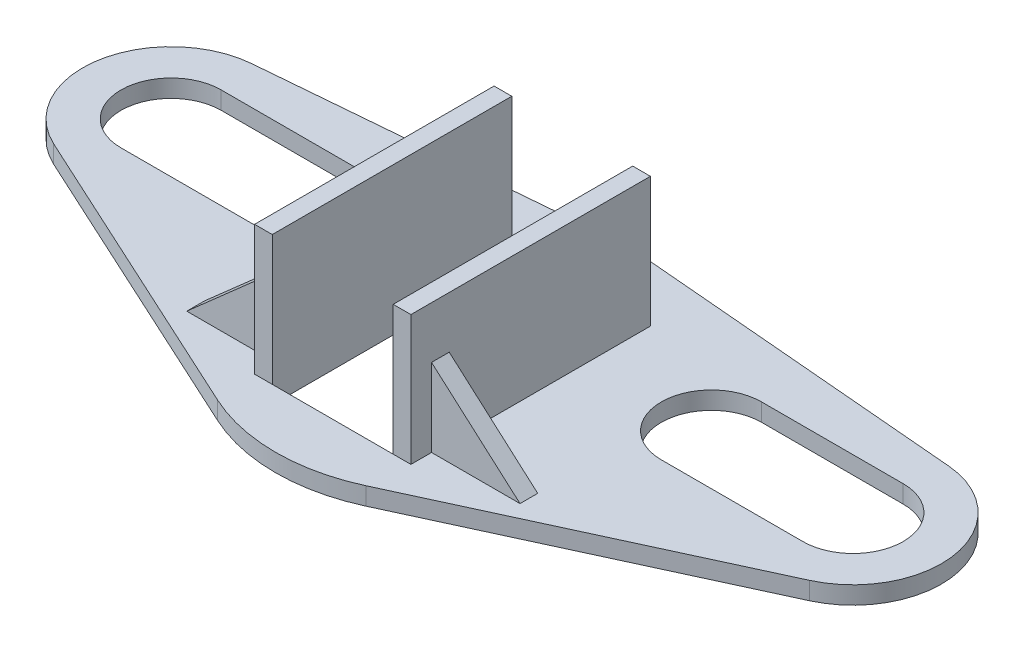
SolidWorks part; units mm, degrees
ref_plane "Front Plane" through (0, 0, 0) normal (0, 0, 1) x (1, 0, 0)
ref_plane "Top Plane" through (0, 0, 0) normal (0, 1, 0) x (1, 0, 0)
ref_plane "Right Plane" through (0, 0, 0) normal (1, 0, 0) x (0, 0, -1)
sketch "Sketch1" plane through (0, 0, 0) normal (0, 1, 0) x (1, 0, 0)
  line L0 (-57.8, 10.1) -> (-33.8, 10.1) construction
  line L1 (-10.25, -20.3) -> (10.25, -20.3)
  line L2 (-10.25, -20.3) -> (-10.25, 20.3)
  line L3 (-10.25, 20.3) -> (10.25, 20.3)
  line L4 (10.25, -20.3) -> (10.25, 20.3)
  line L5 (-10.25, -20.3) -> (10.25, 20.3) construction
  line L6 (-10.25, 20.3) -> (10.25, -20.3) construction
  line L7 (-57.8, 18.6) -> (-33.8, 18.6)
  line L8 (-57.8, 1.6) -> (-33.8, 1.6)
  line L9 (33.8, 10.1) -> (57.8, 10.1) construction
  line L10 (33.8, 18.6) -> (57.8, 18.6)
  line L11 (33.8, 1.6) -> (57.8, 1.6)
  line L12 (-59.0812, 25.0452) -> (-2.5624, 29.8904)
  line L13 (2.5624, 29.8904) -> (59.0812, 25.0452)
  line L14 (12.5472, -27.2501) -> (64.0736, -3.5251)
  line L15 (-64.0736, -3.5251) -> (-12.5472, -27.2501)
  arc A0 (-57.8, 18.6) -> (-57.8, 1.6) centre (-57.8, 10.1) ccw
  arc A1 (-33.8, 1.6) -> (-33.8, 18.6) centre (-33.8, 10.1) ccw
  arc A2 (33.8, 18.6) -> (33.8, 1.6) centre (33.8, 10.1) ccw
  arc A3 (57.8, 1.6) -> (57.8, 18.6) centre (57.8, 10.1) ccw
  arc A4 (-12.5472, -27.2501) -> (12.5472, -27.2501) centre (0, 0) ccw
  arc A5 (-59.0812, 25.0452) -> (-64.0736, -3.5251) centre (-57.8, 10.1) ccw
  arc A6 (64.0736, -3.5251) -> (59.0812, 25.0452) centre (57.8, 10.1) ccw
  arc A7 (2.5624, 29.8904) -> (-2.5624, 29.8904) centre (0, 0) ccw
  point P0 (0, 0)
  point P8 (-45.8, 10.1)
  point P13 (45.8, 10.1)
  dimension "D8" = 60
  dimension "D9" = 30
  dimension "D1" = 20.5
  dimension "D2" = 40.6
  dimension "D3" = 17
  dimension "D4" = 24
  dimension "D5" = 91.6
  dimension "D6" = 45.8
  dimension "D7" = 10.1
extrude "Boss-Extrude1" add sketch "Sketch1" along normal blind 3
sketch "Sketch2" plane through (0, 3, 0) normal (0, 1, 0) x (1, 0, 0)
  line L0 (10.25, 20.3) -> (-10.25, 20.3) construction
  line L1 (-10.25, -20.3) -> (-13.25, -20.3)
  line L2 (-10.25, -20.3) -> (-10.25, 20.3)
  line L3 (-10.25, 20.3) -> (-13.25, 20.3)
  line L4 (-13.25, -20.3) -> (-13.25, 20.3)
  line L6 (10.25, -20.3) -> (13.25, -20.3)
  line L7 (10.25, -20.3) -> (10.25, 20.3)
  line L8 (10.25, 20.3) -> (13.25, 20.3)
  line L9 (13.25, -20.3) -> (13.25, 20.3)
  dimension "D1" = 3
  dimension "D2" = 3
extrude "Boss-Extrude2" add sketch "Sketch2" along normal blind 22
ref_plane "Plane1" through (0, 0, 15.3) normal (0, 0, 1) x (1, 0, 0)
sketch "Sketch3" plane through (0, 0, 15.3) normal (0, 0, 1) x (1, 0, 0)
  line L0 (13.25, 16.2288) -> (28.25, 3)
  line L1 (13.25, 25) -> (13.25, 3) construction
  line L2 (12.5472, 3) -> (64.0736, 3) construction
  dimension "D1" = 20
  dimension "D2" = 15
rib "Rib1" sketch "Sketch3" sketch "Sketch3" thickness 3 extrusion direction parallel to sketch draft on no parameters "D1"=3
mirror "Mirror1" about plane through (0, 0, 0) normal (1, 0, 0) of "Rib1"
sketch "Sketch4" plane through (0, 0, 0) normal (0, -1, 0) x (1, 0, 0)
  circle A0 centre (0, -10.1) radius 7.5 construction
  dimension "D1" = 15
  dimension "D2" = 10.1
